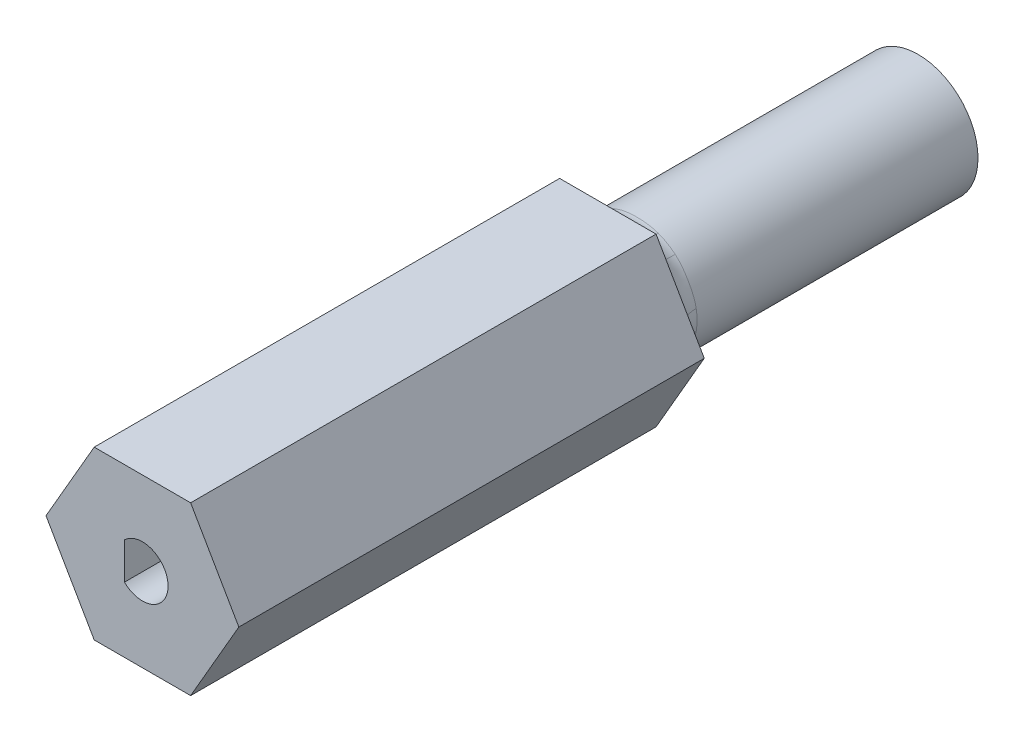
SolidWorks part; units mm, degrees
ref_plane "Front Plane" through (0, 0, 0) normal (0, 0, 1) x (1, 0, 0)
ref_plane "Top Plane" through (0, 0, 0) normal (0, 1, 0) x (1, 0, 0)
ref_plane "Right Plane" through (0, 0, 0) normal (1, 0, 0) x (0, 0, -1)
sketch "Sketch1" plane through (0, 0, 0) normal (0, 0, 1) x (1, 0, 0)
  line L1 (3.9465, 6.8355) -> (-3.9465, 6.8355)
  line L2 (-3.9465, 6.8355) -> (-7.893, 0)
  line L3 (-7.893, 0) -> (-3.9465, -6.8355)
  line L4 (-3.9465, -6.8355) -> (3.9465, -6.8355)
  line L5 (3.9465, -6.8355) -> (7.893, 0)
  line L6 (7.893, 0) -> (3.9465, 6.8355)
  circle A0 centre (0, 0) radius 6.8355 construction
  circle A1 centre (0, 0) radius 4.9
  dimension "D2" = 9.8
  dimension "D1" = 15.786
extrude "Boss-Extrude1" add sketch "Sketch1" along normal blind 38.1 contours L1 L2 L3 L4 L5 L6
extrude "Boss-Extrude2" add sketch "Sketch1<3>" against normal blind 25.4 contours A1 region at (0, 0, 0)
sketch "Sketch1<3>" plane through (0, 0, 0) normal (0, 0, 1) x (1, 0, 0) same geometry as "Sketch1"
sketch "Sketch2" plane through (0, 0, 38.1) normal (0, 0, 1) x (1, 0, 0)
  line L0 (-1.4697, 1.5) -> (-1.4697, -1.5)
  circle A0 centre (0, 0) radius 2.1
  point P5 (-0.4515, 1.2183)
  dimension "D1" = 4.2
  dimension "D2" = 3
extrude "Cut-Extrude1" cut sketch "Sketch2" against normal blind 15 contours L0 A0 region at (0.1793, 0, 38.1)
fillet "Fillet1" radius 2.4 1 edges at (4.9, 0, 0)
